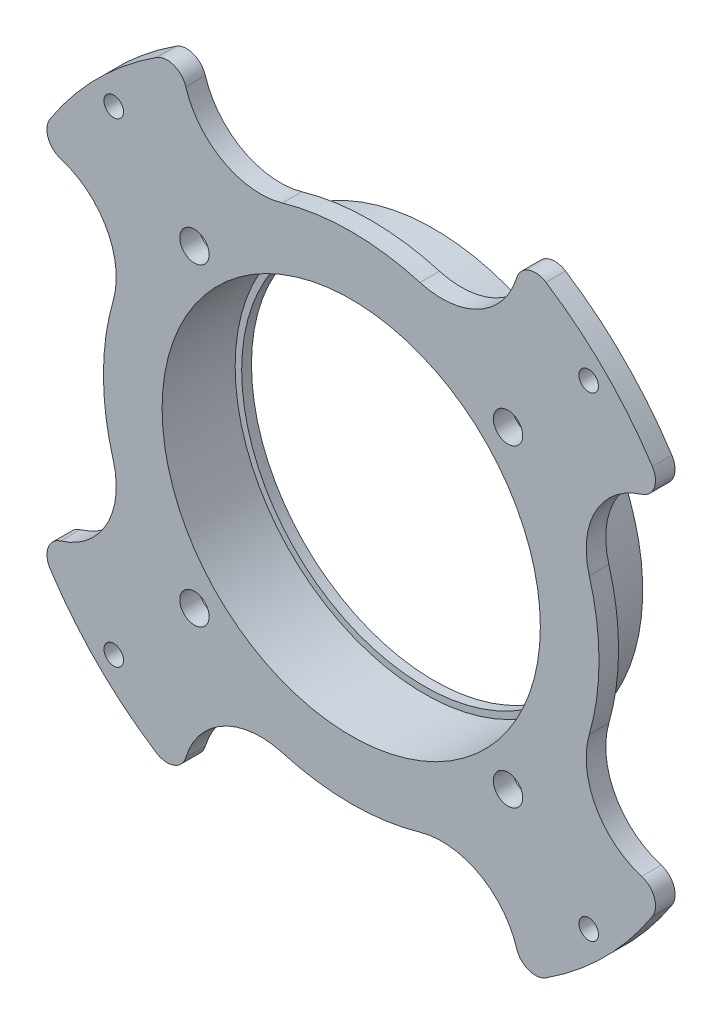
SolidWorks part; units mm, degrees
material "6061 合金"
ref_plane "前视基准面" through (0, 0, 0) normal (0, 0, 1) x (1, 0, 0)
ref_plane "上视基准面" through (0, 0, 0) normal (0, 1, 0) x (1, 0, 0)
ref_plane "右视基准面" through (0, 0, 0) normal (1, 0, 0) x (0, 0, -1)
sketch "草图1" plane through (0, 0, 0) normal (0, 0, 1) x (1, 0, 0)
  line L0 (0, 0) -> (24.2773, 24.2773) construction
  line L1 (0, 0) -> (0, 37.5) construction
  line L2 (29.1937, 23.5368) -> (36.6515, 30.9946)
  line L3 (23.5368, 29.1937) -> (30.9946, 36.6515)
  line L10 (0, 0) -> (33.9411, 33.9411) construction
  line L11 (23.5368, -29.1937) -> (30.9946, -36.6515)
  line L12 (29.1937, -23.5368) -> (36.6515, -30.9946)
  line L13 (0, 0) -> (33.9411, -33.9411) construction
  line L14 (-29.1937, -23.5368) -> (-36.6515, -30.9946)
  line L15 (-23.5368, -29.1937) -> (-30.9946, -36.6515)
  line L16 (0, 0) -> (-33.9411, -33.9411) construction
  line L17 (-23.5368, 29.1937) -> (-30.9946, 36.6515)
  line L18 (-29.1937, 23.5368) -> (-36.6515, 30.9946)
  line L19 (0, 0) -> (-33.9411, 33.9411) construction
  circle A0 centre (0, 0) radius 30
  arc A1 (23.5368, 29.1937) -> (-23.5368, 29.1937) centre (0, 0) ccw
  arc A2 (34.5223, 28.8654) -> (28.8654, 34.5223) centre (0, 0) ccw
  arc A4 (-29.1937, 23.5368) -> (-29.1937, -23.5368) centre (0, 0) ccw
  arc A5 (28.8654, -34.5223) -> (34.5223, -28.8654) centre (0, 0) ccw
  arc A6 (-23.5368, -29.1937) -> (23.5368, -29.1937) centre (0, 0) ccw
  arc A7 (30.9946, -36.6515) -> (36.6515, -30.9946) centre (0, 0) ccw
  arc A8 (29.1937, -23.5368) -> (29.1937, 23.5368) centre (0, 0) ccw
  arc A9 (-34.5223, -28.8654) -> (-28.8654, -34.5223) centre (0, 0) ccw
  arc A11 (36.6515, 30.9946) -> (30.9946, 36.6515) centre (0, 0) ccw
  arc A14 (-36.6515, -30.9946) -> (-30.9946, -36.6515) centre (0, 0) ccw
  arc A15 (-28.8654, 34.5223) -> (-34.5223, 28.8654) centre (0, 0) ccw
  arc A16 (-30.9946, 36.6515) -> (-36.6515, 30.9946) centre (0, 0) ccw
  point P27 (0, 1.4142)
  point P43 (0, 0)
  dimension "D1" = 45
  dimension "D2" = 4
  dimension "D3" = 4
  dimension "D4" = 4
extrude "凸台-拉伸1" add sketch "草图1" along normal blind 3 contours A1 A0 | L2 A2 L3 A1 | L2 L3 A2 | A1 | A1 | A1 region at (36.4393, 0, 0) region at (32.8398, 32.8398, 0)
extrude "凸台-拉伸3" add sketch "草图1<3>" along normal blind 4 contours L2 L3 A2 | L11 A7 L12 A5 | L14 A14 L15 A9 | L17 A16 L18 A15 region at (32.8398, 32.8398, 0) region at (32.8398, -32.8398, 0) region at (-32.8398, 32.8398, 0) region at (-32.8398, -32.8398, 0)
sketch "草图1<3>" plane through (0, 0, 0) normal (0, 0, 1) x (1, 0, 0) same geometry as "草图1"
sketch "草图3" plane through (0, 0, 4) normal (0, 0, 1) x (1, 0, 0)
  line L0 (28.8654, -34.5223) -> (35.9595, -41.6163)
  line L1 (41.6163, -35.9595) -> (34.5223, -28.8654)
  line L2 (-34.5223, -28.8654) -> (-41.6163, -35.9595)
  line L3 (-35.9595, -41.6163) -> (-28.8654, -34.5223)
  line L6 (34.5223, 28.8654) -> (36.6515, 30.9946)
  line L7 (30.9946, 36.6515) -> (28.8654, 34.5223)
  line L8 (34.5223, 28.8654) -> (41.6163, 35.9595)
  line L9 (35.9595, 41.6163) -> (28.8654, 34.5223)
  line L10 (-28.8654, 34.5223) -> (-35.9595, 41.6163)
  line L11 (-41.6163, 35.9595) -> (-34.5223, 28.8654)
  arc A1 (41.6163, 35.9595) -> (35.9595, 41.6163) centre (0, 0) ccw
  arc A2 (35.9595, -41.6163) -> (41.6163, -35.9595) centre (0, 0) ccw
  arc A3 (28.8654, -34.5223) -> (34.5223, -28.8654) centre (0, 0) ccw
  arc A6 (36.6515, 30.9946) -> (30.9946, 36.6515) centre (0, 0) ccw
  arc A7 (34.5223, 28.8654) -> (28.8654, 34.5223) centre (0, 0) ccw
  arc A9 (34.5223, 28.8654) -> (28.8654, 34.5223) centre (0, 0) ccw
  arc A10 (-41.6163, -35.9595) -> (-35.9595, -41.6163) centre (0, 0) ccw
  arc A11 (-34.5223, -28.8654) -> (-28.8654, -34.5223) centre (0, 0) ccw
  arc A14 (-35.9595, 41.6163) -> (-41.6163, 35.9595) centre (0, 0) ccw
  arc A15 (-28.8654, 34.5223) -> (-34.5223, 28.8654) centre (0, 0) ccw
  point P21 (0, 0)
  dimension "D1" = 4
  dimension "D2" = 0
extrude "凸台-拉伸4" add sketch "草图3" against normal blind 3
fillet "圆角1" radius 8 8 edges at (23.5368, 29.1937, 1.5) (29.1937, 23.5368, 1.5) (29.1937, -23.5368, 1.5) (23.5368, -29.1937, 1.5) (-23.5368, -29.1937, 1.5) (-23.5368, 29.1937, 1.5) (-29.1937, 23.5368, 1.5) (-29.1937, -23.5368, 1.5)
fillet "圆角2" radius 3 4 edges at (33.9411, 33.9411, 0) (33.9411, -33.9411, 0) (-33.9411, 33.9411, 0) (-33.9411, -33.9411, 0)
sketch "草图4" plane through (0, 0, 0) normal (0, 0, -1) x (-1, 0, 0)
  line L0 (0, 0) -> (36.416, 36.416) construction
  line L1 (0, 0) -> (0, 45.586) construction
  circle A0 centre (0, 0) radius 51.5 construction
  circle A1 centre (36.416, 36.416) radius 1.5
  circle A2 centre (36.416, -36.416) radius 1.5
  circle A3 centre (-36.416, -36.416) radius 1.5
  circle A4 centre (-36.416, 36.416) radius 1.5
  point P13 (0, 0)
  dimension "D1" = 4
  dimension "D2" = 45
extrude "切除-拉伸1" cut sketch "草图4" against normal blind 42
sketch "草图5" plane through (0, 0, 0) normal (0, 0, -1) x (-1, 0, 0)
  line L0 (0, 0) -> (24.0416, 24.0416) construction
  circle A0 centre (0, 0) radius 34 construction
  circle A13 centre (24.0416, 24.0416) radius 2.25
  circle A14 centre (24.0416, -24.0416) radius 2.25
  circle A15 centre (-24.0416, -24.0416) radius 2.25
  circle A16 centre (-24.0416, 24.0416) radius 2.25
  point P17 (0, 0)
  point P35 (0, 0)
  dimension "D2" = 4.5
  dimension "D3" = 4
extrude "切除-拉伸2" cut sketch "草图5" against normal blind 32
ref_plane "基准面1" through (0, 0, -8.6) normal (0, 0, -1) x (-1, 0, 0)
sketch "草图8" plane through (0, 0, -8.6) normal (0, 0, -1) x (-1, 0, 0)
  line L0 (0, 0) -> (0, 34) construction
  line L2 (7, 12.1244) -> (17.25, 29.8779)
  line L3 (12.1244, 7) -> (29.8779, 17.25)
  line L5 (0, 0) -> (26.5165, -26.5165) construction
  line L9 (12.1244, -7) -> (29.8779, -17.25)
  line L10 (0, 0) -> (-24.3952, -24.3952) construction
  line L11 (0, 0) -> (26.5165, 26.5165) construction
  line L12 (7, -12.1244) -> (17.25, -29.8779)
  line L13 (-12.1244, -7) -> (-29.8779, -17.25)
  line L14 (-7, -12.1244) -> (-17.25, -29.8779)
  line L15 (0, 0) -> (-26.5165, 26.5165) construction
  line L17 (-12.1244, 7) -> (-29.8779, 17.25)
  line L19 (0, 0) -> (14, 0) construction
  line L23 (-7, 12.1244) -> (-17.25, 29.8779)
  line L24 (21.4022, 27.0591) -> (23.5368, 29.1937)
  line L25 (27.0591, 21.4022) -> (29.1937, 23.5368)
  line L26 (-27.0591, 21.4022) -> (-29.1937, 23.5368)
  line L27 (-21.4022, 27.0591) -> (-23.5368, 29.1937)
  line L28 (-27.0591, -21.4022) -> (-29.1937, -23.5368)
  line L30 (21.4022, -27.0591) -> (23.5368, -29.1937)
  line L31 (27.0591, -21.4022) -> (29.1937, -23.5368)
  circle A0 centre (0, 0) radius 10.5
  arc A2 (23.5368, -29.1937) -> (29.1937, -23.5368) centre (0, 0) ccw
  arc A5 (29.1937, 23.5368) -> (23.5368, 29.1937) centre (0, 0) ccw
  arc A6 (25.9808, 15) -> (15, 25.9808) centre (0, 0) ccw
  arc A7 (11.4805, -27.7164) -> (25.9808, -15) centre (0, 0) ccw
  arc A8 (21.4022, -27.0591) -> (29.8779, -17.25) centre (0, 0) ccw
  arc A12 (29.8779, 17.25) -> (17.25, 29.8779) centre (0, 0) ccw
  arc A14 (-25.9808, -15) -> (-15, -25.9808) centre (0, 0) ccw
  circle A15 centre (0, 0) radius 14
  arc A16 (-27.0591, -21.4022) -> (-17.25, -29.8779) centre (0, 0) ccw
  arc A17 (-23.5368, 29.1937) -> (-29.1937, 23.5368) centre (0, 0) ccw
  arc A18 (-15, 25.9808) -> (-25.9808, 15) centre (0, 0) ccw
  arc A19 (-21.4022, 27.0591) -> (-29.8779, 17.25) centre (0, 0) ccw
  arc A22 (-17.25, 29.8779) -> (-21.4022, 27.0591) centre (0, 0) ccw
  arc A23 (17.25, -29.8779) -> (21.4022, -27.0591) centre (0, 0) ccw
  arc A24 (-29.1937, -23.5368) -> (-23.5368, -29.1937) centre (0, 0) ccw [skipped]
  arc A25 (-29.8779, -17.25) -> (-27.0591, -21.4022) centre (0, 0) ccw
  point P33 (0, 0)
  point P46 (0, 0)
  dimension "D2" = 4
  dimension "D3" = 30
extrude "凸台-拉伸5" add sketch "草图8" along normal blind 8 separate body contours A0 region at (-9.6195, 9.6195, -8.6)
extrude "凸台-拉伸6" add sketch "草图8<3>" along normal blind 4 contours A18 | A19 A18 | A14 | A16 A14 | A6 | A12 A6 | A7 | A8 A7 region at (-16.0571, 16.0571, -8.6) region at (-22.5812, 22.5812, -8.6) region at (16.0571, 16.0571, -8.6) region at (22.5812, 22.5812, -8.6) region at (-16.0571, -16.0571, -8.6) region at (16.0571, -16.0571, -8.6) region at (-22.5812, -22.5812, -8.6) region at (22.5812, -22.5812, -8.6)
sketch "草图8<3>" plane through (0, 0, -8.6) normal (0, 0, -1) x (-1, 0, 0) same geometry as "草图8"
extrude "凸台-拉伸7" add sketch "草图8<4>" against normal blind 9 contours A12 A6 | A8 A7 | A16 A14 | A19 A18 region at (-22.5812, 22.5812, -8.6) region at (22.5812, 22.5812, -8.6) region at (-22.5812, -22.5812, -8.6) region at (22.5812, -22.5812, -8.6)
sketch "草图8<4>" plane through (0, 0, -8.6) normal (0, 0, -1) x (-1, 0, 0) same geometry as "草图8"
fillet "圆角3" radius 4 4 edges at (24.3952, 24.3952, -12.6) (24.3952, -24.3952, -12.6) (-24.3952, 24.3952, -12.6) (-24.3952, -24.3952, -12.6)
fillet "圆角4" radius 14 8 edges at (-12.1244, 7, -10.6) (12.1244, -7, -10.6) (-12.1244, -7, -10.6) (12.1244, 7, -10.6) (-7, 12.1244, -10.6) (7, -12.1244, -10.6) (-7, -12.1244, -10.6) (7, 12.1244, -10.6)
sketch "草图9" plane through (0, 0, 0) normal (0, 0, -1) x (-1, 0, 0)
  circle A0 centre (0, 0) radius 37.5
  circle A1 centre (0, 0) radius 48
extrude "凸台-拉伸8" add sketch "草图9" against normal blind 3
sketch "草图10" plane through (0, 0, 0) normal (0, 0, -1) x (-1, 0, 0)
  line L0 (19, 32.909) -> (24, 41.5692)
  line L11 (32.909, 19) -> (41.5692, 24)
  line L12 (32.909, -19) -> (41.5692, -24)
  line L13 (19, -32.909) -> (24, -41.5692)
  line L14 (-19, -32.909) -> (-24, -41.5692)
  line L15 (-32.909, -19) -> (-41.5692, -24)
  line L16 (-32.909, 19) -> (-41.5692, 24)
  line L17 (-19, 32.909) -> (-24, 41.5692)
  arc A0 (-32.909, 19) -> (-32.909, -19) centre (0, 0) ccw
  arc A2 (-41.5692, 24) -> (-41.5692, -24) centre (0, 0) ccw
  arc A5 (41.5692, -24) -> (41.5692, 24) centre (0, 0) ccw
  arc A6 (32.909, -19) -> (32.909, 19) centre (0, 0) ccw
  arc A7 (-19, -32.909) -> (19, -32.909) centre (0, 0) ccw
  arc A8 (-24, -41.5692) -> (24, -41.5692) centre (0, 0) ccw
  arc A10 (19, 32.909) -> (-19, 32.909) centre (0, 0) ccw
  arc A12 (-24, 41.5692) -> (24, 41.5692) centre (0, 0) cw
  point P17 (0, 0)
  point P38 (0, 0)
  dimension "D1" = 60
  dimension "D4" = 4
extrude "切除-拉伸3" cut sketch "草图10" against normal blind 3
fillet "圆角5" radius 12 8 edges at (32.909, 19, 1.5) (32.909, -19, 1.5) (19, -32.909, 1.5) (-19, -32.909, 1.5) (-32.909, -19, 1.5) (-32.909, 19, 1.5) (19, 32.909, 1.5) (-19, 32.909, 1.5)
sketch "草图11" plane through (0, 0, 0) normal (0, 0, -1) x (-1, 0, 0)
  arc A0 (-22.0753, 39.258) -> (-39.258, 22.0753) centre (0, 0) ccw
  arc A1 (-24, 41.5692) -> (-41.5692, 24) centre (0, 0) ccw
  arc A2 (36.5045, -10.5557) -> (41.5692, -24) centre (48.0322, -13.8891) ccw construction
  arc A3 (24, -41.5692) -> (10.5557, -36.5045) centre (13.8891, -48.0322) ccw construction
  arc A4 (-10.5557, -36.5045) -> (-24, -41.5692) centre (-13.8891, -48.0322) ccw construction
  arc A5 (-41.5692, -24) -> (-36.5045, -10.5557) centre (-48.0322, -13.8891) ccw construction
  arc A6 (-36.5045, 10.5557) -> (-41.5692, 24) centre (-48.0322, 13.8891) ccw construction
  arc A7 (-24, 41.5692) -> (-10.5557, 36.5045) centre (-13.8891, 48.0322) ccw construction
  arc A8 (41.5692, 24) -> (36.5045, 10.5557) centre (48.0322, 13.8891) ccw construction
  arc A18 (-39.258, -22.0753) -> (-22.0753, -39.258) centre (0, 0) ccw
  arc A19 (-41.5692, -24) -> (-24, -41.5692) centre (0, 0) ccw
  arc A20 (39.258, 22.0753) -> (22.0753, 39.258) centre (0, 0) ccw
  arc A21 (41.5692, 24) -> (24, 41.5692) centre (0, 0) ccw
  arc A22 (22.0753, -39.258) -> (39.258, -22.0753) centre (0, 0) ccw
  arc A23 (24, -41.5692) -> (41.5692, -24) centre (0, 0) ccw
  arc A24 (10.5557, 36.5045) -> (24, 41.5692) centre (13.8891, 48.0322) ccw construction
  arc A25 (22.0753, 39.258) -> (24, 41.5692) centre (13.8891, 48.0322) ccw
  arc A40 (39.258, -22.0753) -> (41.5692, -24) centre (48.0322, -13.8891) ccw
  arc A41 (24, -41.5692) -> (22.0753, -39.258) centre (13.8891, -48.0322) ccw
  arc A42 (-22.0753, -39.258) -> (-24, -41.5692) centre (-13.8891, -48.0322) ccw
  arc A43 (-41.5692, -24) -> (-39.258, -22.0753) centre (-48.0322, -13.8891) ccw
  arc A44 (-39.258, 22.0753) -> (-41.5692, 24) centre (-48.0322, 13.8891) ccw
  arc A45 (-24, 41.5692) -> (-22.0753, 39.258) centre (-13.8891, 48.0322) ccw
  arc A46 (41.5692, 24) -> (39.258, 22.0753) centre (48.0322, 13.8891) ccw
extrude "凸台-拉伸9" add sketch "草图11" against normal up to surface (4 mm away) up to face at (-34.916, 36.416, 4)
sketch "草图12" plane through (0, 0, 4) normal (0, 0, 1) x (1, 0, 0)
  line L0 (-36.6515, -30.9946) -> (-41.6163, -35.9595) construction
  line L1 (36.6515, -30.9946) -> (41.6163, -35.9595) construction
  line L2 (30.9946, -36.6515) -> (35.9595, -41.6163) construction
  line L3 (36.6515, 30.9946) -> (41.6163, 35.9595) construction
  line L4 (30.9946, 36.6515) -> (35.9595, 41.6163) construction
  line L5 (-30.9946, 36.6515) -> (-35.9595, 41.6163) construction
  line L6 (-36.6515, 30.9946) -> (-41.6163, 35.9595) construction
  line L7 (-36.6515, -30.9946) -> (-41.6163, -35.9595)
  line L8 (36.6515, -30.9946) -> (41.6163, -35.9595)
  line L9 (30.9946, -36.6515) -> (35.9595, -41.6163)
  line L10 (36.6515, 30.9946) -> (41.6163, 35.9595)
  line L11 (30.9946, 36.6515) -> (35.9595, 41.6163)
  line L12 (-30.9946, 36.6515) -> (-35.9595, 41.6163)
  line L13 (-36.6515, 30.9946) -> (-41.6163, 35.9595)
  line L14 (-30.9946, -36.6515) -> (-35.9595, -41.6163) construction
  line L15 (-30.9946, -36.6515) -> (-35.9595, -41.6163)
  line L16 (0, 0) -> (-36.416, 36.416) construction
  arc A0 (-30.9946, -36.6515) -> (-24, -41.5692) centre (0, 0) ccw
  arc A1 (-35.9595, -41.6163) -> (-25.8787, -48.5313) centre (0, 0) ccw
  arc A2 (-24, 41.5692) -> (-25.8787, 48.5313) centre (-13.8891, 48.0322) cw
  arc A18 (25.8787, -48.5313) -> (35.9595, -41.6163) centre (0, 0) ccw
  arc A19 (24, -41.5692) -> (30.9946, -36.6515) centre (0, 0) ccw
  arc A20 (41.6163, -35.9595) -> (48.5313, -25.8787) centre (0, 0) ccw
  arc A21 (36.6515, -30.9946) -> (41.5692, -24) centre (0, 0) ccw
  arc A22 (41.5692, 24) -> (24, 41.5692) centre (0, 0) ccw
  arc A23 (48.5313, 25.8787) -> (25.8787, 48.5313) centre (0, 0) ccw
  arc A24 (-24, 41.5692) -> (-41.5692, 24) centre (0, 0) ccw
  arc A25 (-25.8787, 48.5313) -> (-48.5313, 25.8787) centre (0, 0) ccw
  arc A26 (-41.5692, -24) -> (-36.6515, -30.9946) centre (0, 0) ccw
  arc A27 (-48.5313, -25.8787) -> (-41.6163, -35.9595) centre (0, 0) ccw
  arc A28 (39.258, -22.0753) -> (41.5692, -24) centre (48.0322, -13.8891) ccw construction
  arc A29 (24, -41.5692) -> (22.0753, -39.258) centre (13.8891, -48.0322) ccw construction
  arc A30 (-22.0753, -39.258) -> (-24, -41.5692) centre (-13.8891, -48.0322) ccw construction
  arc A31 (-41.5692, -24) -> (-39.258, -22.0753) centre (-48.0322, -13.8891) ccw construction
  arc A32 (-39.258, 22.0753) -> (-41.5692, 24) centre (-48.0322, 13.8891) ccw construction
  arc A34 (41.5692, 24) -> (39.258, 22.0753) centre (48.0322, 13.8891) ccw construction
  arc A35 (22.0753, 39.258) -> (24, 41.5692) centre (13.8891, 48.0322) ccw construction
  arc A36 (41.5692, -24) -> (48.5313, -25.8787) centre (48.0322, -13.8891) ccw
  arc A37 (25.8787, -48.5313) -> (24, -41.5692) centre (13.8891, -48.0322) ccw
  arc A38 (-24, -41.5692) -> (-25.8787, -48.5313) centre (-13.8891, -48.0322) ccw
  arc A39 (-48.5313, -25.8787) -> (-41.5692, -24) centre (-48.0322, -13.8891) ccw
  arc A40 (-41.5692, 24) -> (-48.5313, 25.8787) centre (-48.0322, 13.8891) ccw
  arc A42 (48.5313, 25.8787) -> (41.5692, 24) centre (48.0322, 13.8891) ccw
  arc A43 (24, 41.5692) -> (25.8787, 48.5313) centre (13.8891, 48.0322) ccw
  line M3 (35.9595, 41.6163) -> (30.9946, 36.6515)
  line M9 (36.6515, 30.9946) -> (41.6163, 35.9595)
extrude "凸台-拉伸10" add sketch "草图12" against normal blind 3 contours L13 A25 A24 | A25 L12 A24 | A23 M3 | A23 M9 | A21 L8 A20 | A19 A18 L9 | A0 L15 A1 | A27 L7 A26 region at (-42.3194, -29.5744, 4) region at (42.3194, -29.5744, 4) region at (29.5744, -42.3194, 4) region at (42.3194, 29.5744, 4) region at (29.5744, 42.3194, 4) region at (-29.5744, 42.3194, 4) region at (-42.3194, 29.5744, 4) region at (-29.5744, -42.3194, 4)
fillet "圆角6" radius 3 8 edges at (-48.5313, -25.8787, 2.5) (-25.8787, -48.5313, 2.5) (25.8787, -48.5313, 2.5) (48.5313, -25.8787, 2.5) (48.5313, 25.8787, 2.5) (25.8787, 48.5313, 2.5) (-25.8787, 48.5313, 2.5) (-48.5313, 25.8787, 2.5)
sketch "草图13" plane through (0, 0, 0) normal (0, 0, -1) x (-1, 0, 0)
  circle A0 centre (0, 0) radius 38
extrude "切除-拉伸4" cut sketch "草图13" along normal blind 46
sketch "草图14" plane through (0, 0, 0) normal (0, 0, -1) x (-1, 0, 0)
  circle A2 centre (0, 0) radius 29
  circle A3 centre (0, 0) radius 30
  dimension "D1" = 58
extrude "凸台-拉伸12" add sketch "草图14" against normal blind 3
sketch "草图15" plane through (0, 0, 0) normal (0, 0, -1) x (-1, 0, 0)
  circle A0 centre (0, 0) radius 29
  circle A1 centre (0, 0) radius 32
  dimension "D1" = 58
  dimension "D2" = 64
extrude "凸台-拉伸13" add sketch "草图15" along normal blind 10.2
sketch "草图18" plane through (0, 0, -10.2) normal (0, 0, -1) x (-1, 0, 0)
  circle A0 centre (0, 0) radius 29
  circle A1 centre (0, 0) radius 28
  dimension "D1" = 56
extrude "凸台-拉伸14" add sketch "草图18" against normal blind 2
sketch "草图19" plane through (0, 0, 1) normal (0, 0, -1) x (-1, 0, 0)
  circle A0 centre (36.416, 36.416) radius 1.5 construction
  circle A1 centre (36.416, 36.416) radius 1.5
  circle A2 centre (-36.416, 36.416) radius 1.5 construction
  circle A3 centre (-36.416, 36.416) radius 1.5
  circle A4 centre (-36.416, -36.416) radius 1.5 construction
  circle A5 centre (-36.416, -36.416) radius 1.5
  arc A6 (46.1832, 29.8682) -> (29.8682, 46.1832) centre (0, 0) ccw
  arc A7 (29.8682, 46.1832) -> (25.3691, 44.5378) centre (28.239, 43.6641) ccw
  arc A8 (24, 41.5692) -> (25.3691, 44.5378) centre (13.8891, 48.0322) ccw
  arc A9 (41.5692, 24) -> (24, 41.5692) centre (0, 0) ccw
  arc A10 (44.5378, 25.3691) -> (41.5692, 24) centre (48.0322, 13.8891) ccw
  arc A11 (44.5378, 25.3691) -> (46.1832, 29.8682) centre (43.6641, 28.239) ccw
  arc A12 (46.1832, 29.8682) -> (29.8682, 46.1832) centre (0, 0) ccw
  arc A13 (29.8682, 46.1832) -> (25.3691, 44.5378) centre (28.239, 43.6641) ccw
  arc A14 (24, 41.5692) -> (25.3691, 44.5378) centre (13.8891, 48.0322) ccw
  arc A15 (41.5692, 24) -> (24, 41.5692) centre (0, 0) ccw
  arc A16 (44.5378, 25.3691) -> (41.5692, 24) centre (48.0322, 13.8891) ccw
  arc A17 (44.5378, 25.3691) -> (46.1832, 29.8682) centre (43.6641, 28.239) ccw
  arc A18 (-29.8682, 46.1832) -> (-46.1832, 29.8682) centre (0, 0) ccw
  arc A19 (-46.1832, 29.8682) -> (-44.5378, 25.3691) centre (-43.6641, 28.239) ccw
  arc A20 (-41.5692, 24) -> (-44.5378, 25.3691) centre (-48.0322, 13.8891) ccw
  arc A21 (-24, 41.5692) -> (-41.5692, 24) centre (0, 0) ccw
  arc A22 (-25.3691, 44.5378) -> (-24, 41.5692) centre (-13.8891, 48.0322) ccw
  arc A23 (-25.3691, 44.5378) -> (-29.8682, 46.1832) centre (-28.239, 43.6641) ccw
  arc A24 (-29.8682, 46.1832) -> (-46.1832, 29.8682) centre (0, 0) ccw
  arc A25 (-46.1832, 29.8682) -> (-44.5378, 25.3691) centre (-43.6641, 28.239) ccw
  arc A26 (-41.5692, 24) -> (-44.5378, 25.3691) centre (-48.0322, 13.8891) ccw
  arc A27 (-24, 41.5692) -> (-41.5692, 24) centre (0, 0) ccw
  arc A28 (-25.3691, 44.5378) -> (-24, 41.5692) centre (-13.8891, 48.0322) ccw
  arc A29 (-25.3691, 44.5378) -> (-29.8682, 46.1832) centre (-28.239, 43.6641) ccw
  arc A30 (-46.1832, -29.8682) -> (-29.8682, -46.1832) centre (0, 0) ccw
  arc A31 (-29.8682, -46.1832) -> (-25.3691, -44.5378) centre (-28.239, -43.6641) ccw
  arc A32 (-24, -41.5692) -> (-25.3691, -44.5378) centre (-13.8891, -48.0322) ccw
  arc A33 (-41.5692, -24) -> (-24, -41.5692) centre (0, 0) ccw
  arc A34 (-44.5378, -25.3691) -> (-41.5692, -24) centre (-48.0322, -13.8891) ccw
  arc A35 (-44.5378, -25.3691) -> (-46.1832, -29.8682) centre (-43.6641, -28.239) ccw
  arc A36 (-46.1832, -29.8682) -> (-29.8682, -46.1832) centre (0, 0) ccw
  arc A37 (-29.8682, -46.1832) -> (-25.3691, -44.5378) centre (-28.239, -43.6641) ccw
  arc A38 (-24, -41.5692) -> (-25.3691, -44.5378) centre (-13.8891, -48.0322) ccw
  arc A39 (-41.5692, -24) -> (-24, -41.5692) centre (0, 0) ccw
  arc A40 (-44.5378, -25.3691) -> (-41.5692, -24) centre (-48.0322, -13.8891) ccw
  arc A41 (-44.5378, -25.3691) -> (-46.1832, -29.8682) centre (-43.6641, -28.239) ccw
  arc A42 (29.8682, -46.1832) -> (46.1832, -29.8682) centre (0, 0) ccw
  arc A43 (46.1832, -29.8682) -> (44.5378, -25.3691) centre (43.6641, -28.239) ccw
  arc A44 (41.5692, -24) -> (44.5378, -25.3691) centre (48.0322, -13.8891) ccw
  arc A45 (24, -41.5692) -> (41.5692, -24) centre (0, 0) ccw
  arc A46 (25.3691, -44.5378) -> (24, -41.5692) centre (13.8891, -48.0322) ccw
  arc A47 (25.3691, -44.5378) -> (29.8682, -46.1832) centre (28.239, -43.6641) ccw
  arc A48 (29.8682, -46.1832) -> (46.1832, -29.8682) centre (0, 0) ccw
  arc A49 (46.1832, -29.8682) -> (44.5378, -25.3691) centre (43.6641, -28.239) ccw
  arc A50 (41.5692, -24) -> (44.5378, -25.3691) centre (48.0322, -13.8891) ccw
  arc A51 (24, -41.5692) -> (41.5692, -24) centre (0, 0) ccw
  arc A52 (25.3691, -44.5378) -> (24, -41.5692) centre (13.8891, -48.0322) ccw
  arc A53 (25.3691, -44.5378) -> (29.8682, -46.1832) centre (28.239, -43.6641) ccw
  circle A54 centre (36.416, -36.416) radius 1.5 construction
  circle A55 centre (36.416, -36.416) radius 1.5
  dimension "D1" = 0
  dimension "D2" = 0
  dimension "D3" = 0
  dimension "D4" = 0
extrude "凸台-拉伸15" add sketch "草图19" along normal blind 1
sketch "草图20" plane through (0, 0, 3) normal (0, 0, 1) x (1, 0, 0)
  circle A0 centre (0, 0) radius 84.6958
extrude "切除-拉伸6" cut sketch "草图20" along normal blind 10
sketch "草图21" plane through (0, 0, -10.2) normal (0, 0, -1) x (-1, 0, 0)
  circle A0 centre (0, 0) radius 32
extrude "切除-拉伸7" cut sketch "草图21" against normal blind 0.5
sketch "草图22" plane through (0, 0, 0.4) normal (0, 0, 1) x (1, 0, 0)
  arc A2 (-22.7834, 25.9069) -> (-25.9069, 22.7834) centre (0, 0) ccw
  arc A3 (-25.9069, 22.7834) -> (-22.7834, 25.9069) centre (-24.0416, 24.0416) ccw
  arc A4 (-22.7834, 25.9069) -> (-25.9069, 22.7834) centre (0, 0) ccw
  arc A5 (-25.9069, 22.7834) -> (-22.7834, 25.9069) centre (-24.0416, 24.0416) ccw
  arc A6 (-25.9069, -22.7834) -> (-22.7834, -25.9069) centre (0, 0) ccw
  arc A7 (-22.7834, -25.9069) -> (-25.9069, -22.7834) centre (-24.0416, -24.0416) ccw
  arc A8 (-25.9069, -22.7834) -> (-22.7834, -25.9069) centre (0, 0) ccw
  arc A9 (-22.7834, -25.9069) -> (-25.9069, -22.7834) centre (-24.0416, -24.0416) ccw
  arc A10 (22.7834, -25.9069) -> (25.9069, -22.7834) centre (0, 0) ccw
  arc A11 (25.9069, -22.7834) -> (22.7834, -25.9069) centre (24.0416, -24.0416) ccw
  arc A12 (22.7834, -25.9069) -> (25.9069, -22.7834) centre (0, 0) ccw
  arc A13 (25.9069, -22.7834) -> (22.7834, -25.9069) centre (24.0416, -24.0416) ccw
  arc A14 (25.9069, 22.7834) -> (22.7834, 25.9069) centre (0, 0) ccw
  arc A15 (22.7834, 25.9069) -> (25.9069, 22.7834) centre (24.0416, 24.0416) ccw
  arc A16 (25.9069, 22.7834) -> (22.7834, 25.9069) centre (0, 0) ccw
  arc A17 (22.7834, 25.9069) -> (25.9069, 22.7834) centre (24.0416, 24.0416) ccw
  dimension "D1" = 0
  dimension "D2" = 0
  dimension "D3" = 0
  dimension "D4" = 0
extrude "切除-拉伸8" cut sketch "草图22" against normal blind 10
sketch "草图23" plane through (0, 0, 0) normal (0, 0, -1) x (-1, 0, 0)
  circle A0 centre (24.0416, 24.0416) radius 4.5
  circle A1 centre (24.0416, -24.0416) radius 4.5
  circle A2 centre (-24.0416, -24.0416) radius 4.5
  circle A3 centre (-24.0416, 24.0416) radius 4.5
  point P12 (0, 0)
  dimension "D1" = 9
  dimension "D2" = 4
extrude "切除-拉伸9" cut sketch "草图23" along normal blind 17
